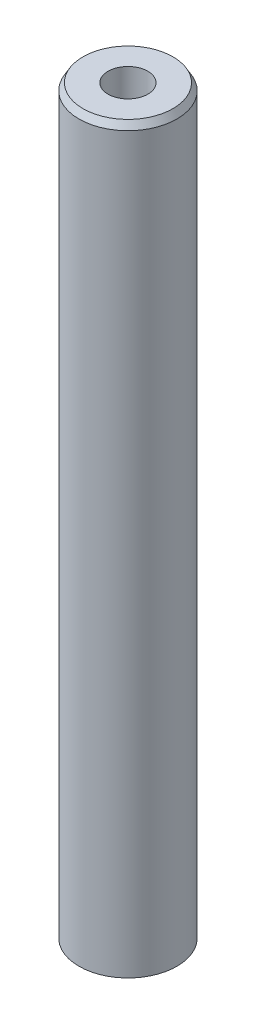
SolidWorks part; units mm, degrees
ref_plane "Front Plane" through (0, 0, 0) normal (0, 0, 1) x (1, 0, 0)
ref_plane "Top Plane" through (0, 0, 0) normal (0, 1, 0) x (1, 0, 0)
ref_plane "Right Plane" through (0, 0, 0) normal (1, 0, 0) x (0, 0, -1)
sketch "Sketch1" plane through (0, 0, 0) normal (0, 1, 0) x (1, 0, 0)
  circle A0 centre (0, 0) radius 7.5
  dimension "SHAFT_OD" = 15
extrude "Boss-Extrude1" add sketch "Sketch1" along normal blind 114.0462
sketch "Sketch2" plane through (0, 0, 0) normal (0, 1, 0) x (1, 0, 0)
  circle A0 centre (0, 0) radius 3.0482
  dimension "BORE_D" = 6.0964
extrude "Cut-Extrude1" cut sketch "Sketch2" along normal through all
chamfer "Chamfer1" distance 1.0659 angle 30 2 edges at (0, 114.0462, 7.5) (0, 0, 7.5) first distance on face at (0, 114.0462, 7.5) first distance on face at (0, 0, 3.0482)
